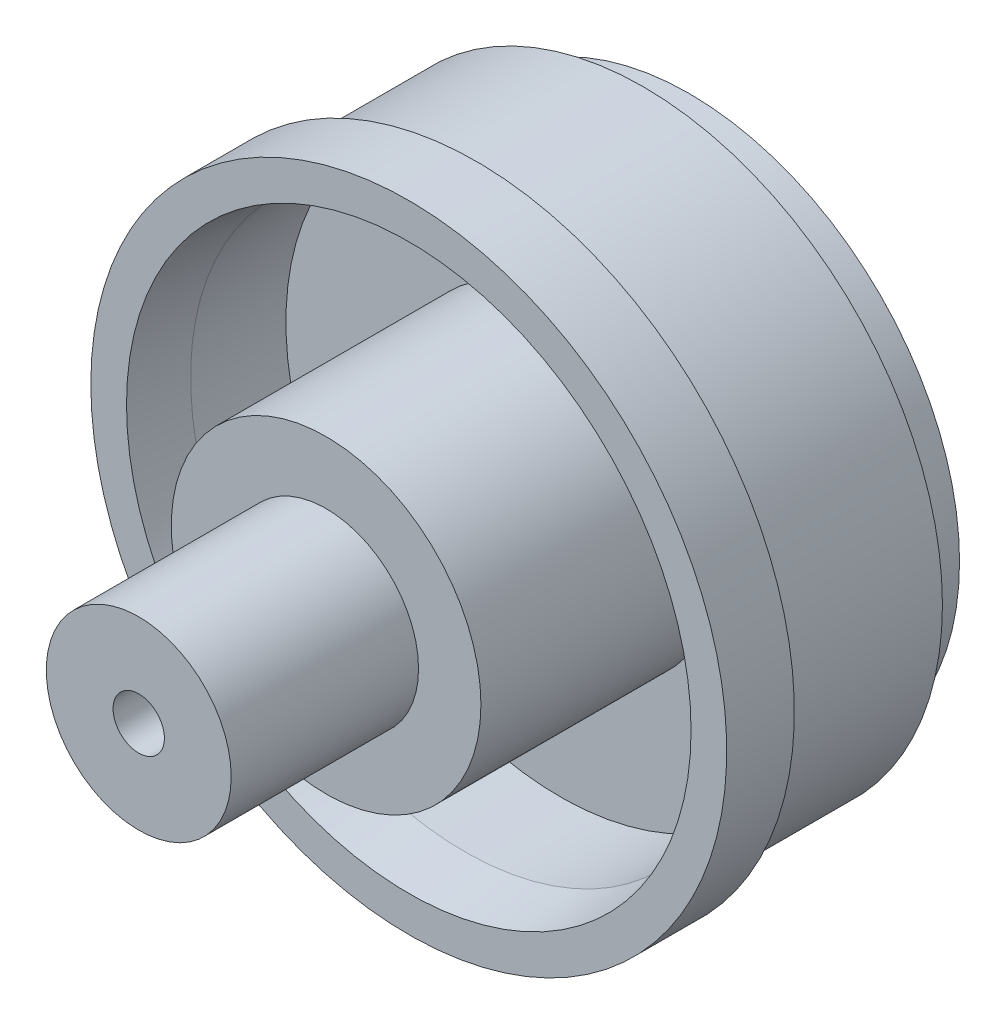
SolidWorks part; units mm, degrees
material "6061-T6 (SS)"
ref_plane "Front Plane" through (0, 0, 0) normal (0, 0, 1) x (1, 0, 0)
ref_plane "Top Plane" through (0, 0, 0) normal (0, 1, 0) x (1, 0, 0)
ref_plane "Right Plane" through (0, 0, 0) normal (1, 0, 0) x (0, 0, -1)
sketch "Sketch1" plane through (0, 0, 0) normal (0, 0, 1) x (1, 0, 0)
  circle A0 centre (0, 0) radius 49.1363
  dimension "D1" = 98.2726
extrude "Extrude1" add sketch "Sketch1" along normal blind 85.09
sketch "Sketch5" plane through (0, 0, 85.09) normal (0, 0, 1) x (1, 0, 0)
  circle A0 centre (0, 0) radius 3.9688
extrude "Extrude5" cut sketch "Sketch5" against normal blind 26.67
sketch "Sketch2" plane through (0, 0, 85.09) normal (0, 0, 1) x (1, 0, 0)
  circle A0 centre (0, 0) radius 14.2875
  dimension "D1" = 28.575
extrude "Extrude2" cut sketch "Sketch2" against normal blind 28.956 flip side to cut
sketch "Sketch3" plane through (0, 0, 56.134) normal (0, 0, 1) x (1, 0, 0)
  circle A0 centre (0, 0) radius 23.9268
  dimension "D1" = 47.8536
extrude "Extrude3" cut sketch "Sketch3" against normal blind 12.7762 flip side to cut
sketch "Sketch4" plane through (0, 0, 0) normal (0, 0, -1) x (-1, 0, 0)
  circle A0 centre (0, 0) radius 46.228
extrude "Extrude4" cut sketch "Sketch4" against normal blind 32.9057 flip side to cut
sketch "Sketch6" plane through (0, 0, 43.3578) normal (0, 0, 1) x (1, 0, 0)
  circle A0 centre (0, 0) radius 42.3545
  circle A1 centre (0, 0) radius 23.9268
  dimension "D1" = 47.8536
  dimension "D2" = 84.709
extrude "Extrude8" cut sketch "Sketch6" against normal blind 23.368
sketch "Sketch7" plane through (0, 0, 0) normal (0, 0, -1) x (-1, 0, 0)
  circle A0 centre (0, 0) radius 19.177
  dimension "D1" = 38.354
extrude "Extrude9" cut sketch "Sketch7" against normal blind 50.8
sketch "Sketch8" plane through (0, 0, 0) normal (0, 0, -1) x (-1, 0, 0)
  circle A0 centre (0, 0) radius 41.7576
  dimension "D1" = 83.5152
extrude "Extrude10" cut sketch "Sketch8" against normal blind 7.112 flip side to cut
chamfer "Chamfer1" distance 1.27 distance2 8.636 1 edges at (42.3545, 0, 43.3578) first distance on face at (42.3545, 0, 43.3578)
